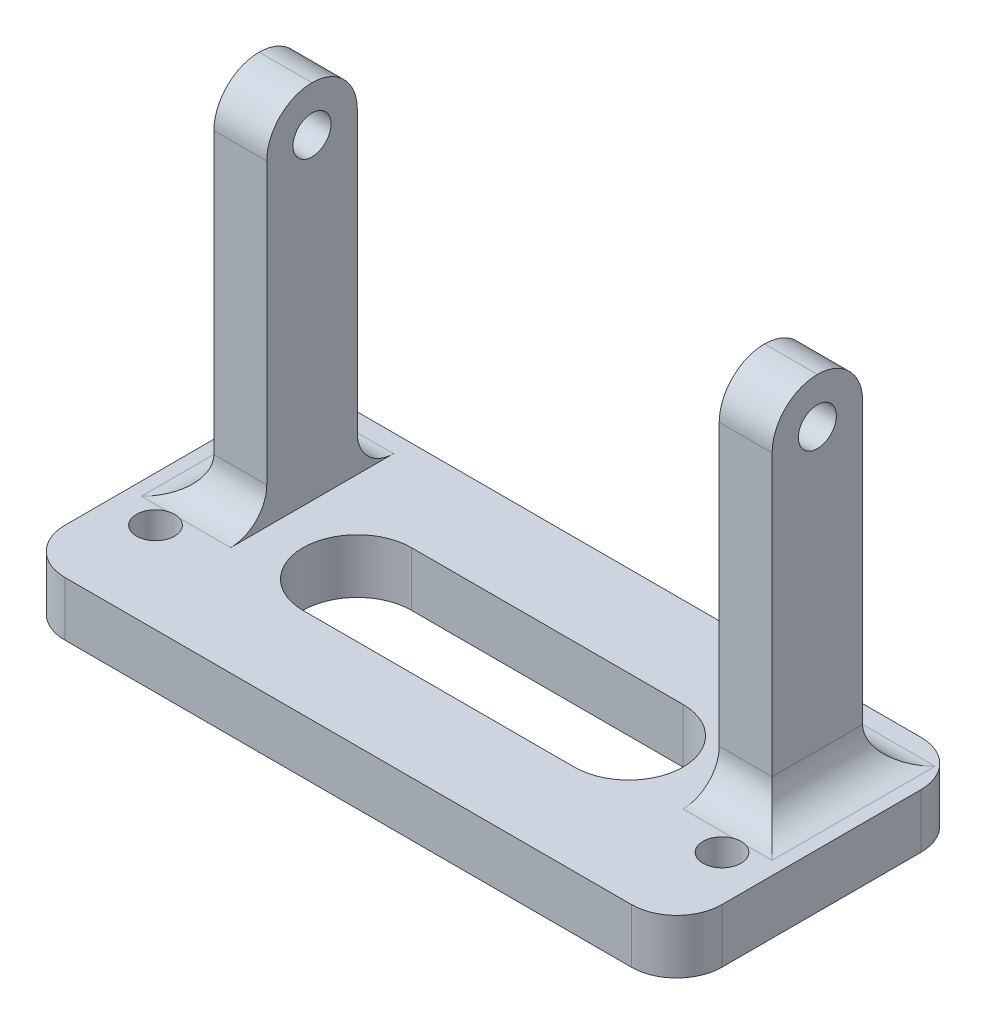
SolidWorks part; units mm, degrees
ref_plane "Płaszczyzna przednia" through (0, 0, 0) normal (0, 0, 1) x (1, 0, 0)
ref_plane "Płaszczyzna górna" through (0, 0, 0) normal (0, 1, 0) x (1, 0, 0)
ref_plane "Płaszczyzna prawa" through (0, 0, 0) normal (1, 0, 0) x (0, 0, -1)
sketch "Szkic1" plane through (0, 0, 0) normal (0, 0, 1) x (1, 0, 0)
  line L7 (6.9437, -9.1674) -> (6.9437, -12.1674)
  line L8 (6.9437, -12.1674) -> (-29.3563, -12.1674)
  line L15 (-29.3563, -12.1674) -> (-29.3563, -9.1674)
  line L18 (1.2937, 10.8326) -> (1.2937, -9.1674)
  line L19 (1.2937, -9.1674) -> (-23.7063, -9.1674)
  line L20 (-23.7063, -9.1674) -> (-23.7063, 10.8326)
  line L25 (-26.6274, -9.1674) -> (-29.3563, -9.1674)
  line L26 (1.2937, 10.8326) -> (4.2149, 10.8326)
  line L27 (4.2149, 10.8326) -> (4.2149, -9.1674)
  line L28 (4.2149, -9.1674) -> (6.9437, -9.1674)
  line L29 (-23.7063, 10.8326) -> (-26.6274, 10.8326)
  line L30 (-26.6274, 10.8326) -> (-26.6274, -9.1674)
  dimension "D1" = 20
  dimension "D2" = 36.3
  dimension "D3" = 3
  dimension "D4" = 25
  dimension "D5" = 2.9212
extrude "Dodanie-wyciągnięcie1" add sketch "Szkic1" along normal blind 5
sketch "Szkic5" plane through (0, 0, 5) normal (0, 0, 1) x (1, 0, 0)
  line L0 (-26.6274, -9.1674) -> (-23.7063, -9.1674)
  line L1 (-23.7063, -9.1674) -> (1.2937, -9.1674)
  line L2 (1.2937, -9.1674) -> (4.2149, -9.1674)
  line L15 (-23.7063, 10.8326) -> (-26.6274, 10.8326)
  line L16 (-26.6274, 10.8326) -> (-26.6274, -9.1674)
  line L17 (-26.6274, -9.1674) -> (-29.3563, -9.1674)
  line L18 (-29.3563, -9.1674) -> (-29.3563, -12.1674)
  line L19 (-29.3563, -12.1674) -> (6.9437, -12.1674)
  line L20 (6.9437, -12.1674) -> (6.9437, -9.1674)
  line L21 (6.9437, -9.1674) -> (4.2149, -9.1674)
  line L22 (4.2149, -9.1674) -> (4.2149, 10.8326)
  line L23 (4.2149, 10.8326) -> (1.2937, 10.8326)
  line L24 (1.2937, 10.8326) -> (1.2937, -9.1674)
  line L25 (1.2937, -9.1674) -> (-23.7063, -9.1674)
  line L26 (-23.7063, -9.1674) -> (-23.7063, 10.8326)
  line L29 (-26.6274, -9.1674) -> (-29.3563, -9.1674)
  line L30 (-29.3563, -9.1674) -> (-29.3563, -12.1674)
  line L31 (-29.3563, -12.1674) -> (6.9437, -12.1674)
  line L32 (6.9437, -12.1674) -> (6.9437, -9.1674)
  line L33 (6.9437, -9.1674) -> (4.2149, -9.1674)
  dimension "D1" = 0
extrude "Dodanie-wyciągnięcie4" add sketch "Szkic5" along normal blind 8
ref_plane "Płaszczyzna1" through (1.2937, -9.1674, 0) normal (-1, 0, 0) x (0, 0, 1)
sketch "Szkic7" plane through (0, 0, 0) normal (0, 0, -1) x (-1, 0, 0)
  line L0 (-4.2149, -9.1674) -> (-1.2937, -9.1674)
  line L1 (-1.2937, -9.1674) -> (23.7063, -9.1674)
  line L3 (23.7063, -9.1674) -> (26.6274, -9.1674)
  line L16 (26.6274, 10.8326) -> (23.7063, 10.8326)
  line L17 (23.7063, 10.8326) -> (23.7063, -9.1674)
  line L18 (23.7063, -9.1674) -> (-1.2937, -9.1674)
  line L19 (-1.2937, -9.1674) -> (-1.2937, 10.8326)
  line L20 (-1.2937, 10.8326) -> (-4.2149, 10.8326)
  line L21 (-4.2149, 10.8326) -> (-4.2149, -9.1674)
  line L22 (-4.2149, -9.1674) -> (-6.9437, -9.1674)
  line L23 (-6.9437, -9.1674) -> (-6.9437, -12.1674)
  line L24 (-6.9437, -12.1674) -> (29.3563, -12.1674)
  line L25 (29.3563, -12.1674) -> (29.3563, -9.1674)
  line L26 (29.3563, -9.1674) -> (26.6274, -9.1674)
  line L27 (26.6274, -9.1674) -> (26.6274, 10.8326)
  line L34 (-4.2149, -9.1674) -> (-6.9437, -9.1674)
  line L35 (-6.9437, -9.1674) -> (-6.9437, -12.1674)
  line L36 (-6.9437, -12.1674) -> (29.3563, -12.1674)
  line L37 (29.3563, -12.1674) -> (29.3563, -9.1674)
  line L38 (29.3563, -9.1674) -> (26.6274, -9.1674)
  dimension "D1" = 0
extrude "Dodanie-wyciągnięcie5" add sketch "Szkic7" along normal blind 3
sketch "Szkic8" plane through (0, -9.1674, 0) normal (0, 1, 0) x (1, 0, 0)
  line L0 (-29.3563, -13) -> (-29.3563, 3) construction
  line L1 (6.9437, -13) -> (6.9437, 3) construction
  circle A0 centre (4.4464, -8) radius 1.05
  circle A2 centre (-26.8536, -8) radius 1.05
  point P10 (-29.3563, -5)
  point P13 (6.9437, -5)
  dimension "D1" = 2.1
  dimension "D3" = 3
  dimension "D4" = 3
  dimension "D7" = 31.3
  dimension "D9" = 2.4973
extrude "Wytnij-wyciągnięcie1" cut sketch "Szkic8" against normal through all
sketch "Szkic9" plane through (-26.6274, 0, 0) normal (-1, 0, 0) x (0, 0, 1)
  line L0 (5, 10.8326) -> (0, 10.8326) construction
  line L1 (0, 10.8326) -> (0, -9.1674) construction
  circle A0 centre (2.5, 8.3326) radius 1.05
  dimension "D1" = 2.1
  dimension "D2" = 2.5
  dimension "D3" = 2.5
extrude "Wytnij-wyciągnięcie2" cut sketch "Szkic9" against normal through all
fillet "Zaokrąglenie1" radius 2.5 4 edges at (6.9437, -10.6674, 13) (6.9437, -10.6674, -3) (-29.3563, -10.6674, 13) (-29.3563, -10.6674, -3)
fillet "Zaokrąglenie2" radius 2.5 4 edges at (-25.1669, 10.8326, 5) (-25.1669, 10.8326, 0) (2.7543, 10.8326, 5) (2.7543, 10.8326, 0)
fillet "Zaokrąglenie3" radius 2 6 edges at (-25.1669, -9.1674, 0) (-26.6274, -9.1674, 2.5) (-25.1669, -9.1674, 5) (4.2149, -9.1674, 2.5) (2.7543, -9.1674, 0) (2.7543, -9.1674, 5)
sketch "Szkic10" plane through (0, -9.1674, 0) normal (0, 1, 0) x (1, 0, 0)
  line L0 (-18.7063, -8) -> (-3.7063, -8)
  line L2 (-3.7063, -2) -> (-18.7063, -2)
  line L4 (4.4437, -13) -> (-26.8563, -13) construction
  line L5 (-26.8563, 3) -> (4.4437, 3) construction
  line L7 (-29.3563, -10.5) -> (-29.3563, 0.5) construction
  line L9 (6.9437, -10.5) -> (6.9437, 0.5) construction
  arc A0 (-18.7063, -8) -> (-18.7063, -2) centre (-18.7063, -5) cw
  arc A1 (-3.7063, -8) -> (-3.7063, -2) centre (-3.7063, -5) ccw
  dimension "D5" = 3
  dimension "D6" = 3
  dimension "D8" = 10.65
  dimension "D1" = 6
  dimension "D2" = 15
  dimension "D3" = 5
  dimension "D4" = 5
  dimension "D7" = 10.65
extrude "Wytnij-wyciągnięcie3" cut sketch "Szkic10" against normal through all
